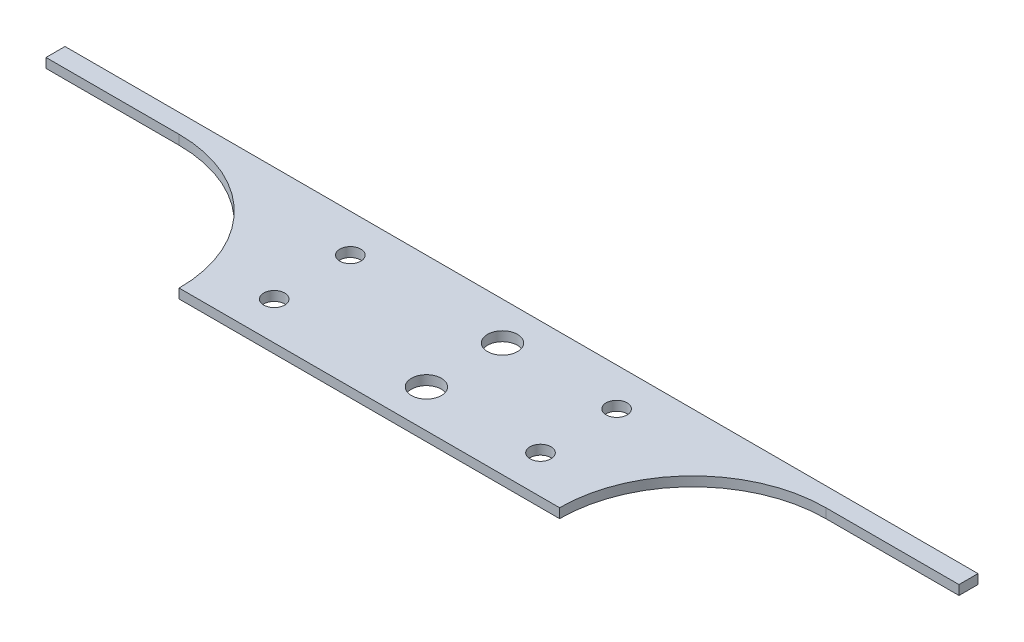
SolidWorks part; units mm, degrees
ref_plane "Front Plane" through (0, 0, 0) normal (0, 0, 1) x (1, 0, 0)
ref_plane "Top Plane" through (0, 0, 0) normal (0, 1, 0) x (1, 0, 0)
ref_plane "Right Plane" through (0, 0, 0) normal (1, 0, 0) x (0, 0, -1)
sketch "Sketch1" plane through (0, 0, 0) normal (0, 1, 0) x (1, 0, 0)
  line L0 (-107.95, 19.05) -> (-152.4, 19.05)
  line L1 (-152.4, -25.4) -> (152.4, -25.4)
  line L2 (-152.4, -25.4) -> (-152.4, 25.4)
  line L3 (-152.4, 25.4) -> (152.4, 25.4)
  line L4 (152.4, -25.4) -> (152.4, 25.4)
  line L5 (-152.4, -25.4) -> (152.4, 25.4) construction
  line L6 (-152.4, 25.4) -> (152.4, -25.4) construction
  line L7 (152.4, 19.05) -> (107.95, 19.05)
  line L8 (44.45, 12.7) -> (6.35, 12.7) construction
  line L9 (-44.45, -12.7) -> (44.45, -12.7) construction
  line L10 (-44.45, -12.7) -> (-44.45, 12.7) construction
  line L11 (-44.45, 12.7) -> (44.45, 12.7) construction
  line L12 (44.45, -12.7) -> (44.45, 12.7) construction
  line L13 (-44.45, -12.7) -> (44.45, 12.7) construction
  line L14 (-44.45, 12.7) -> (44.45, -12.7) construction
  arc A0 (-107.95, 19.05) -> (-63.5, -25.4) centre (-107.95, -25.4) cw
  arc A1 (107.95, 19.05) -> (63.5, -25.4) centre (107.95, -25.4) ccw
  circle A2 centre (-44.45, 12.7) radius 3.5
  circle A3 centre (-44.45, -12.7) radius 3.5
  circle A4 centre (44.45, 12.7) radius 3.5
  circle A5 centre (44.45, -12.7) radius 3.5
  circle A6 centre (6.35, 12.7) radius 5
  circle A7 centre (6.35, -12.7) radius 5
  point P0 (0, 0)
  point P14 (0, 0)
  dimension "D4" = 44.45
  dimension "D8" = 7
  dimension "D9" = 10
  dimension "D1" = 50.8
  dimension "D2" = 304.8
  dimension "D3" = 44.45
  dimension "D5" = 88.9
  dimension "D6" = 25.4
  dimension "D7" = 38.1
extrude "Boss-Extrude1" add sketch "Sketch1" along normal blind 3.175 contours L0 A0 L1 L4 L3 L2 region at (-0.1229, 0, -4.044)
